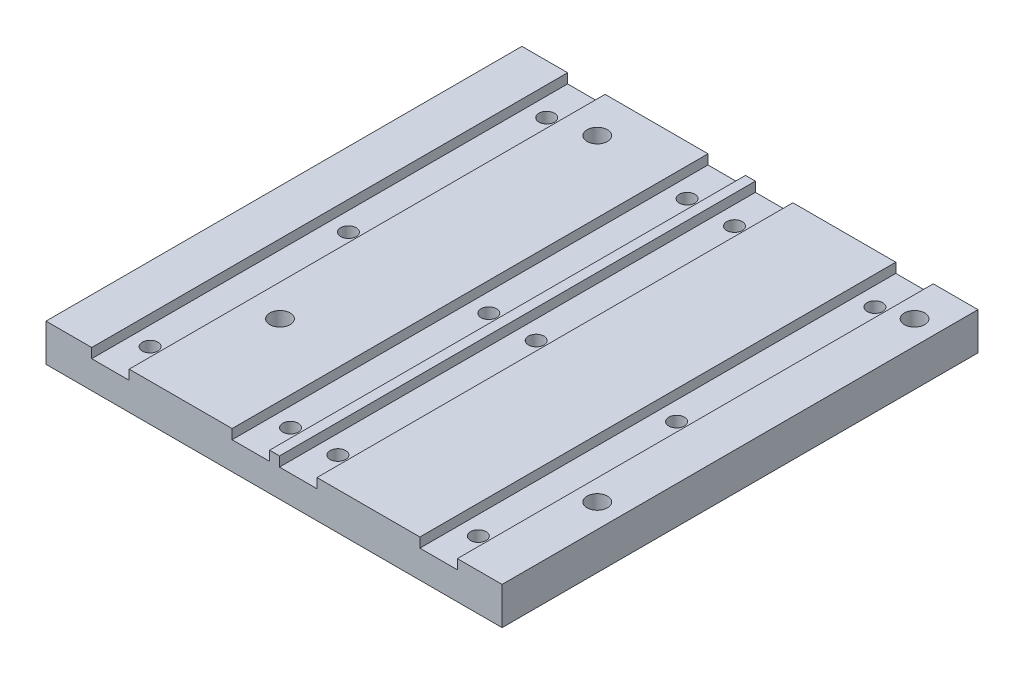
SolidWorks part; units mm, degrees
ref_plane "Front Plane" through (0, 0, 0) normal (0, 0, 1) x (1, 0, 0)
ref_plane "Top Plane" through (0, 0, 0) normal (0, 1, 0) x (1, 0, 0)
ref_plane "Right Plane" through (0, 0, 0) normal (1, 0, 0) x (0, 0, -1)
sketch "Sketch1" plane through (0, 0, 0) normal (0, 1, 0) x (1, 0, 0)
  line L1 (73.025, 76.2) -> (-73.025, 76.2)
  line L2 (73.025, 76.2) -> (73.025, -76.2)
  line L3 (73.025, -76.2) -> (-73.025, -76.2)
  line L4 (-73.025, 76.2) -> (-73.025, -76.2)
  line L5 (73.025, 76.2) -> (-73.025, -76.2) construction
  line L6 (73.025, -76.2) -> (-73.025, 76.2) construction
  line L7 (-36.195, 63.5) -> (65.405, 63.5) construction
  line L8 (-36.195, 63.5) -> (-36.195, -38.1) construction
  line L9 (-36.195, -38.1) -> (65.405, -38.1) construction
  line L10 (65.405, 63.5) -> (65.405, -38.1) construction
  line L11 (-36.195, 63.5) -> (65.405, -38.1) construction
  line L12 (-36.195, -38.1) -> (65.405, 63.5) construction
  point P0 (0, 0)
  point P6 (14.605, 12.7)
  point P11 (85.5348, 53.8017)
  point P12 (13.2411, 0)
  point P13 (13.2411, 0)
  point P14 (0, 0)
  point P15 (0, 0)
  dimension "D1" = 152.4
  dimension "D2" = 146.05
  dimension "D3" = 101.6
  dimension "D4" = 7.62
  dimension "D5" = 12.7
extrude "Boss-Extrude1" add sketch "Sketch1" against normal blind 12
hole_wizard "1/4 Clearance Hole1" positions "Sketch2" profile "Sketch3" hole size "1/4" standard "ANSI Inch" end condition through all
sketch "Sketch2" plane through (0, 0, 0) normal (0, 1, 0) x (1, 0, 0)
  point P0 (-36.195, 63.5)
  point P3 (-36.195, -38.1)
  point P6 (65.405, -38.1)
  point P9 (65.405, 63.5)
sketch "Sketch3" plane through (-36.195, 0, -63.5) normal (1, 0, 0) x (0, 0, 1)
  line L0 (0, 0) -> (0, 12)
  line L1 (0, 12) -> (3.2639, 12)
  line L2 (3.2639, 12) -> (3.2639, 0)
  line L5 (3.2639, 0) -> (0, 0)
  line L11 (0, -6.35) -> (0, 107.95) construction
  dimension "Thru Hole Dia." = 6.5278
  dimension "Thru Hole Depth" = 12
sketch "Sketch4" plane through (0, 0, 76.2) normal (0, 0, 1) x (1, 0, 0)
  line L0 (-73.025, 0) -> (73.025, 0) construction
  line L1 (46.705, -3.11) -> (58.705, -3.11)
  line L2 (46.705, -3.11) -> (46.705, 0)
  line L3 (46.705, 0) -> (58.705, 0)
  line L4 (58.705, -3.11) -> (58.705, 0)
  line L5 (46.705, -3.11) -> (58.705, 0) construction
  line L6 (46.705, 0) -> (58.705, -3.11) construction
  line L7 (73.025, -12) -> (73.025, 0) construction
  line L8 (-73.025, -12) -> (73.025, -12) construction
  point P0 (52.705, -1.555)
  dimension "D1" = 8.89
  dimension "D2" = 12
  dimension "D3" = 20.32
extrude "Cut-Extrude1" cut sketch "Sketch4" against normal through all
sketch "Sketch6" plane through (0, -12, 0) normal (0, -1, 0) x (1, 0, 0)
  line L0 (52.705, 63.5) -> (52.705, -63.5) construction
  line L1 (46.705, 76.2) -> (58.705, 76.2) construction
  line L2 (73.025, 76.2) -> (73.025, -76.2) construction
  line L3 (46.705, -76.2) -> (-73.025, -76.2) construction
  point P5 (52.705, 76.2)
  point P8 (73.025, 0)
  point P10 (52.705, 0)
  dimension "D1" = 12.7
hole_wizard "CBORE for #10 Socket Head Cap Screw1" positions "Sketch9" profile "Sketch8" counterbore size "#10" standard "ANSI Inch" end condition through all
sketch "Sketch9" plane through (0, -12, 0) normal (0, -1, 0) x (-1, 0, 0)
  point P0 (-52.705, -63.5)
  point P3 (-52.705, 63.5)
  point P7 (-52.705, 0)
sketch "Sketch8" plane through (52.705, -12, 63.5) normal (1, 0, 0) x (0, 0, -1)
  line L0 (0, 0) -> (0, 12)
  line L1 (0, 12) -> (2.4892, 12)
  line L3 (2.4892, 12) -> (2.4892, 5.08)
  line L4 (2.4892, 5.08) -> (4.7625, 5.08)
  line L5 (4.7625, 5.08) -> (4.7625, 0)
  line L7 (4.7625, 0) -> (0, 0)
  line L11 (0, -6.35) -> (0, 107.95) construction
  dimension "Thru Hole Dia." = 4.9784
  dimension "Thru Hole Depth" = 12
  dimension "C'Bore Dia." = 9.525
  dimension "C'Bore Depth" = 5.08
pattern_linear "LPattern1" count 2 spacing 44.958 along (-1, 0, 0) count 2 spacing 60.133 along (-1, 0, 0) of "Cut-Extrude1", "CBORE for #10 Socket Head Cap Screw1"
